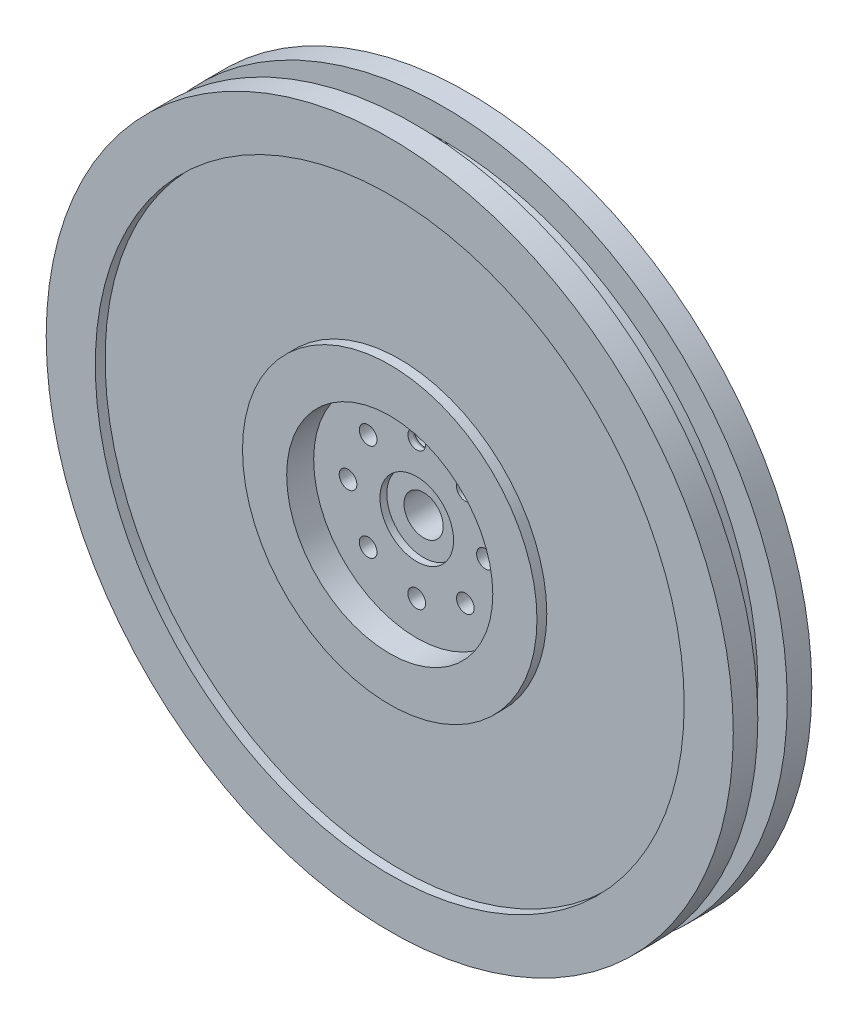
SolidWorks part; units mm, degrees
ref_plane "Front Plane" through (0, 0, 0) normal (0, 0, 1) x (1, 0, 0)
ref_plane "Top Plane" through (0, 0, 0) normal (0, 1, 0) x (1, 0, 0)
ref_plane "Right Plane" through (0, 0, 0) normal (1, 0, 0) x (0, 0, -1)
sketch "Sketch2" plane through (0, 0, 0) normal (0, 1, 0) x (1, 0, 0)
  line L0 (0, -27.7721) -> (0, 23.9685) construction
  line L1 (0, 0) -> (35, 0)
  line L2 (35, 0) -> (35, 2.5)
  line L3 (35, 2.5) -> (32, 2.5)
  line L4 (32, 2.5) -> (32, 5.5)
  line L5 (32, 5.5) -> (35, 5.5)
  line L6 (35, 5.5) -> (35, 8)
  line L7 (35, 8) -> (0, 8)
  line L8 (0, 8) -> (0, 0)
  point P11 (0, 4)
  point P12 (32, 4)
  dimension "D1" = 8
  dimension "D2" = 35
  dimension "D3" = 3
  dimension "D4" = 3
revolve "Revolve1" add sketch "Sketch2" angle 360 about L0
sketch "Sketch3" plane through (0, 0, 0) normal (0, 0, 1) x (1, 0, 0)
  circle A0 centre (0, 0) radius 7.375 construction
  circle A1 centre (0, 7.375) radius 1.25
  circle A2 centre (5.2149, 5.2149) radius 1.25
  circle A3 centre (7.375, 0) radius 1.25
  circle A4 centre (5.2149, -5.2149) radius 1.25
  circle A5 centre (0, -7.375) radius 1.25
  circle A6 centre (-5.2149, -5.2149) radius 1.25
  circle A7 centre (-7.375, 0) radius 1.25
  circle A8 centre (-5.2149, 5.2149) radius 1.25
  point P21 (0, 0)
  dimension "D1" = 8
extrude "Cut-Extrude1" [suppressed] cut sketch "Sketch3" against normal blind 5
sketch "Sketch4" plane through (0, 0, 0) normal (0, 0, 1) x (1, 0, 0)
  circle A0 centre (0, 0) radius 10.5
extrude "Cut-Extrude2" cut sketch "Sketch4" against normal blind 2.75
sketch "Sketch5" plane through (0, 0, -2.75) normal (0, 0, 1) x (1, 0, 0)
  circle A0 centre (0, 0) radius 3.75
extrude "Cut-Extrude3" cut sketch "Sketch5" against normal blind 0.7
sketch "Sketch6" plane through (0, 0, -2.75) normal (0, 0, 1) x (1, 0, 0)
  circle A0 centre (0, 0) radius 7 construction
  circle A1 centre (0, 7) radius 0.9
  circle A2 centre (4.9497, 4.9497) radius 0.9
  circle A3 centre (7, 0) radius 0.9
  circle A4 centre (4.9497, -4.9497) radius 0.9
  circle A5 centre (0, -7) radius 0.9
  circle A6 centre (-4.9497, -4.9497) radius 0.9
  circle A7 centre (-7, 0) radius 0.9
  circle A8 centre (-4.9497, 4.9497) radius 0.9
  point P22 (0, 0)
  dimension "D1" = 8
extrude "Cut-Extrude4" cut sketch "Sketch6" against normal through all
ref_axis "Axis1" through (-7, 0, -8) along (0, 0, 1)
ref_axis "Axis2" through (7, 0, -8) along (0, 0, 1)
ref_plane "Plane2" through (0, 0, 0) normal (0, -1, 0) x (-1, 0, 0)
ref_plane "Plane3" through (0, 35, 0) normal (0, 1, 0) x (1, 0, 0)
sketch "Sketch11" plane through (0, 0, -3.45) normal (0, 0, 1) x (1, 0, 0)
  circle A0 centre (0, 0) radius 2
extrude "Cut-Extrude8" cut sketch "Sketch11" against normal through all
ref_axis "Axis3" through (0, 0, -8) along (0, 0, 1)
ref_plane "Plane4" through (0, 0, 0) normal (-1, 0, 0) x (0, 0, 1)
ref_plane "Plane5" through (0, 32, 0) normal (0, 1, 0) x (1, 0, 0)
sketch "Sketch14" plane through (0, 32, 0) normal (0, 1, 0) x (1, 0, 0)
  line L0 (-7.0769, 4.5) -> (7.6722, 4.5) construction
  line L1 (-32, 5.5) -> (32, 5.5) construction
  circle A0 centre (0, 4.5) radius 1
  dimension "D1" = 1
extrude "Cut-Extrude9" cut sketch "Sketch14" against normal blind 25
ref_axis "Axis5" through (0, 7, -4.5) along (0, 1, 0)
ref_plane "Plane6" through (0, 0, -4.5) normal (0, 0, 1) x (0, 1, 0)
sketch "Sketch17" plane through (0, 0, -4.5) normal (0, 0, 1) x (0, 1, 0)
  circle A0 centre (7, 0) radius 1
  circle A1 centre (7, 0) radius 0.9 construction
extrude "Cut-Extrude11" cut sketch "Sketch17" against normal blind 1 and the other way blind 1 contours A0
fillet "Fillet4" radius 0.3 2 edges at (0.9, 7, -3.5) (0.9, 7, -5.5)
sketch "Sketch18" plane through (0, 0, -8) normal (0, 0, -1) x (-1, 0, 0)
  circle A1 centre (0, 0) radius 30
extrude "Cut-Extrude12" cut sketch "Sketch18" against normal blind 1
sketch "Sketch19" plane through (0, 0, 0) normal (0, 0, 1) x (1, 0, 0)
  circle A0 centre (0, 0) radius 15
  circle A1 centre (0, 0) radius 30
  dimension "D1" = 15
extrude "Cut-Extrude13" cut sketch "Sketch19" against normal blind 1
